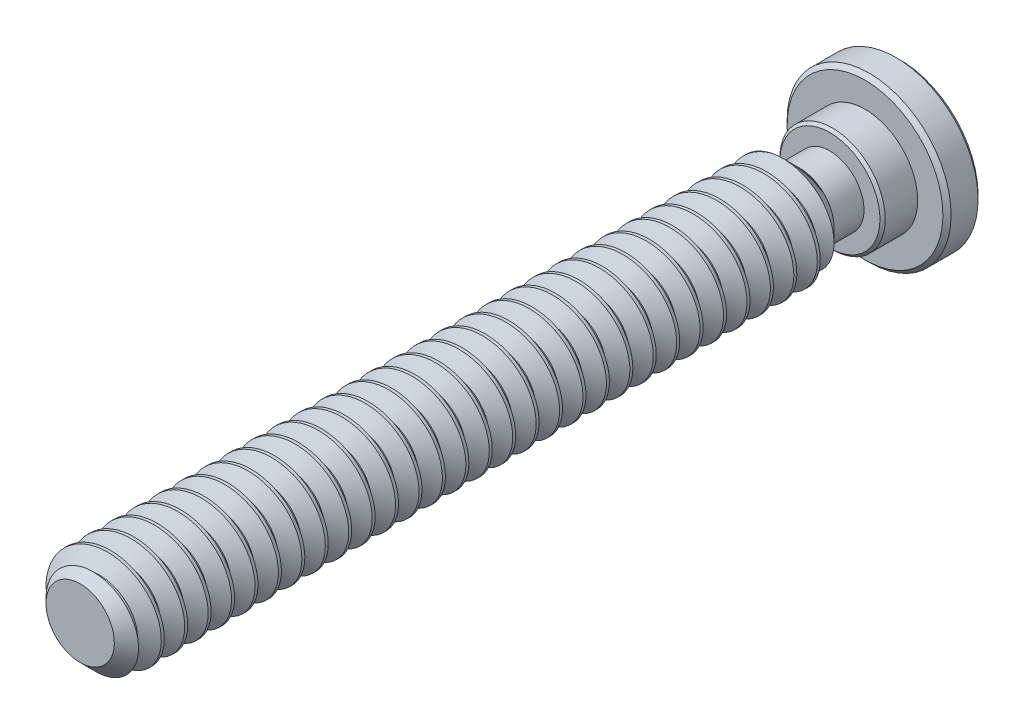
SolidWorks part; units mm, degrees
other "DetailItem1"
ref_plane "Front Plane" through (0, 0, 0) normal (0, 0, 1) x (1, 0, 0)
ref_plane "Top Plane" through (0, 0, 0) normal (0, 1, 0) x (1, 0, 0)
ref_plane "Right Plane" through (0, 0, 0) normal (1, 0, 0) x (0, 0, -1)
sketch "Sketch1" plane through (0, 0, 0) normal (1, 0, 0) x (0, 0, -1)
  line L0 (0, 0) -> (-26.5906, 0) construction
  line L1 (0, 0) -> (1.1906, 0) construction
  line L2 (1.1906, 2.7781) -> (1.1906, -2.7781) construction
  line L3 (-26.5906, 1.7526) -> (-26.5906, -1.7526) construction
  line L4 (0, 1.7859) -> (0, -1.7859) construction
  line L5 (-26.5906, 1.7526) -> (-25.7969, 1.7526) construction
  line L6 (1.1906, 0.7937) -> (1.1906, -0.7938) construction
  line L7 (0, 1.7859) -> (-1.1906, 1.7859) construction
  line L8 (-1.1906, 1.7859) -> (-1.1906, 1.1573) construction
  line L9 (-1.1906, 1.1573) -> (-2.2066, 1.1573) construction
  line L10 (-2.2066, 1.1573) -> (-2.8019, 1.7526) construction
  point P2 (-23.8125, -1.7526)
  point P4 (-1.1906, 0)
  point P8 (1.1906, 0)
  point P11 (-26.5906, 0)
  point P14 (0, 0)
  point P19 (1.1906, 0)
  dimension "Thread Diameter" = 3.5052
  dimension "Head Diameter" = 5.5562
  dimension "Head Height" = 1.1906
  dimension "Shoulder Diameter" = 3.5719
  dimension "Shoulder Length" = 1.1906
  dimension "Thread Pitch" = 0.7937
  dimension "Drive Size" = 1.5875
  dimension "D1" = 2.7781
  dimension "D3" = 2.3146
  dimension "Undercut Length" = 1.016
  dimension "D2" = 45
  dimension "Length" = 25.4
sketch "Sketch13" plane through (0, 0, 0) normal (1, 0, 0) x (0, 0, -1)
  line L0 (1.1906, 2.7781) -> (0, 2.7781)
  line L1 (0, 2.7781) -> (0, 1.7859)
  line L3 (-26.5906, 1.7526) -> (-26.5906, 0)
  line L4 (-26.5906, 0) -> (1.1906, 0)
  line L5 (1.1906, 0) -> (1.1906, 2.7781)
  line L6 (-2.2066, 1.1573) -> (-2.8019, 1.7526) construction
  line L7 (-1.1906, 1.1573) -> (-2.2066, 1.1573) construction
  line L8 (-1.1906, 1.7859) -> (-1.1906, 1.1573) construction
  line L9 (0, 1.7859) -> (-1.1906, 1.7859) construction
  line L10 (-2.2066, 1.1573) -> (-2.8019, 1.7526)
  line L11 (-1.1906, 1.1573) -> (-2.2066, 1.1573)
  line L12 (-1.1906, 1.7859) -> (-1.1906, 1.1573)
  line L13 (0, 1.7859) -> (-1.1906, 1.7859)
  line L14 (-2.8019, 1.7526) -> (-26.5906, 1.7526)
revolve "Revolve1" add sketch "Sketch13" angle 360 about L4
sketch "Sketch2" plane through (0, 0, 26.5906) normal (0, 0, 1) x (1, 0, 0)
  circle A2 centre (0, 0) radius 1.7526
chamfer "Chamfer2" distance 0.5953 angle 45 1 edges at (0, -1.7526, 26.5906)
sketch "Sketch3" plane through (0, 0, 0) normal (1, 0, 0) x (0, 0, -1)
  line L0 (-26.541, 1.8385) -> (-27.3348, 1.8385) construction
  line L1 (-27.3348, 1.8385) -> (-26.9379, 1.1511) construction
  line L2 (-26.9379, 1.1511) -> (-26.541, 1.8385) construction
  line L4 (-26.5906, 1.7526) -> (-27.2852, 1.7526) construction
  line L5 (-26.9379, 1.8385) -> (-26.9379, 1.7526) construction
  line L6 (-27.31, 1.7956) -> (-26.5658, 1.7956)
  line L7 (-26.5658, 1.7956) -> (-27.31, 1.7956) construction
  line L8 (-26.8883, 1.237) -> (-26.9875, 1.237) construction
  line L9 (-26.9379, 1.237) -> (-26.9379, 1.1511) construction
  line L10 (-26.5658, 1.7956) -> (-26.8883, 1.237)
  line L11 (-26.8883, 1.237) -> (-26.9875, 1.237)
  line L12 (-26.9875, 1.237) -> (-27.31, 1.7956)
  point P16 (-26.9379, 1.7956)
  dimension "D1" = 0.7937
  dimension "D2" = 0.0992
sketch "Sketch7" plane through (0, 0, -1.1906) normal (0, 0, -1) x (-1, 0, 0)
  line L1 (0, 0.9165) -> (-0.7937, 0.4583)
  line L2 (-0.7937, 0.4583) -> (-0.7937, -0.4583)
  line L3 (-0.7937, -0.4583) -> (0, -0.9165)
  line L4 (0, -0.9165) -> (0.7937, -0.4583)
  line L5 (0.7937, -0.4583) -> (0.7937, 0.4583)
  line L6 (0.7937, 0.4583) -> (0, 0.9165)
  circle A0 centre (0, 0) radius 0.7937 construction
extrude "Cut-Extrude1" cut sketch "Sketch7" against normal blind 1.1906
chamfer "Chamfer1" distance 0.1389 angle 45 2 edges at (0, -2.7781, -1.1906) (0, -2.7781, 0)
sketch "Sketch8" plane through (0, 0, -1.1906) normal (0, 0, -1) x (-1, 0, 0)
  circle A0 centre (0, 0) radius 0.9165
extrude "Cut-Extrude2" cut sketch "Sketch8" against normal through all draft 45
chamfer "Chamfer3" distance 0.0893 angle 45 1 edges at (0, -1.7859, 1.1906)
curve "Helix/Spiral1" pitch 0.7937 height 25.146 turns 31.68 parameters "pitch"=0.7937
sweep "Cut-Sweep1" cut profiles "Sketch3" path "Helix/Spiral1"
equation "\"D3@Helix/Spiral1\"=\"Length@Sketch1\"- .01"
equation "\"D1@Cut-Extrude1\" = \"Drive Size@Sketch1\" * .75"
equation "\"D1@Chamfer1\"=\"Head Diameter@Sketch1\" * .025"
equation "\"D1@Chamfer2\"=\"pitch@Helix/Spiral1\"*.750"
equation "\"D1@Sketch3\" = \"Thread Pitch@Sketch1\""
equation "\"D2@Sketch3\"=\"D1@Sketch3\"/ 1/8"
equation "\"pitch@Helix/Spiral1\" = \"Thread Pitch@Sketch1\""
equation "\"D1@Sketch1\" = \"Thread Pitch@Sketch1\" * 3.5"
equation "\"D3@Sketch1\"=\"Thread Diameter@Sketch1\" -(\"Thread Pitch@Sketch1\"*1.5)"
equation "\"D1@Chamfer3\"=\"Shoulder Diameter@Sketch1\"*.025"
